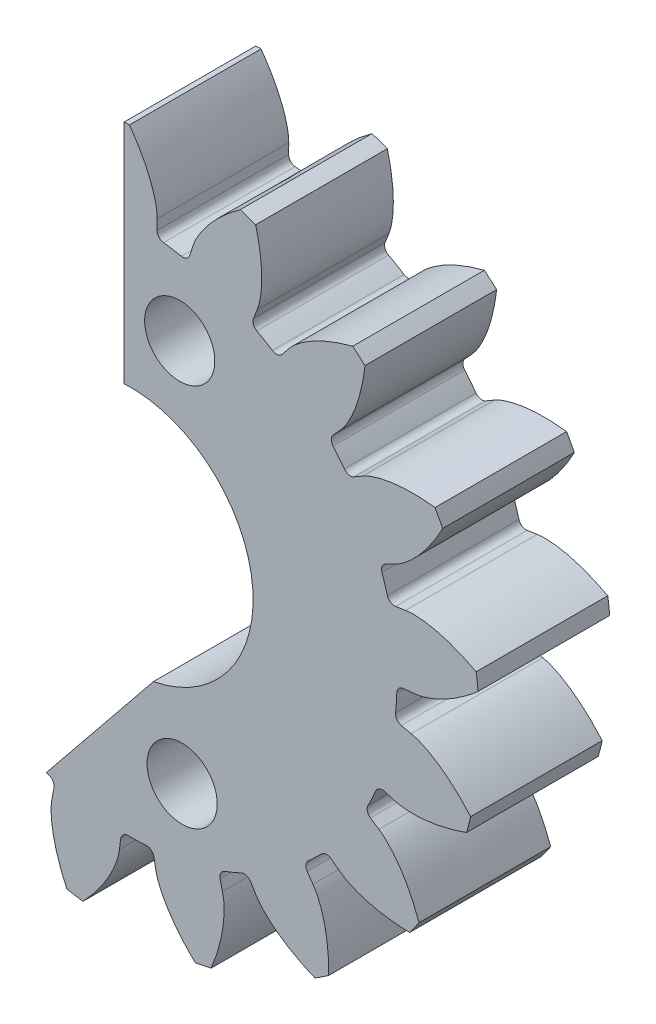
SolidWorks part; units mm, degrees
ref_plane "Front" through (0, 0, 0) normal (0, 0, 1) x (1, 0, 0)
ref_plane "Top" through (0, 0, 0) normal (0, 1, 0) x (1, 0, 0)
ref_plane "Right" through (0, 0, 0) normal (1, 0, 0) x (0, 0, -1)
sketch "Sketch1" plane through (0, 0, 0) normal (0, 0, 1) x (1, 0, 0)
  line L68 (2.1427, 9.4464) -> (2.0368, 9.1165)
  line L69 (0.916, 9.2963) -> (0.9185, 9.6427)
  line L70 (-1.4144, 9.5825) -> (-1.394, 9.2367)
  line L71 (-2.504, 8.9994) -> (-2.6268, 9.3234)
  line L72 (-4.7805, 8.4245) -> (-4.6366, 8.1093)
  line L73 (-5.5859, 7.4871) -> (-5.8174, 7.7449)
  line L74 (-7.501, 6.1287) -> (-7.2529, 5.8868)
  line L75 (-7.9134, 4.9637) -> (-8.2224, 5.1204)
  line L76 (-9.2084, 3.0052) -> (-8.8897, 2.8692)
  line L77 (-9.1721, 1.7699) -> (-9.5168, 1.8043)
  line L78 (-9.6722, -0.5242) -> (-9.3259, -0.5358)
  line L79 (-9.1921, -1.663) -> (-9.526, -1.7554)
  line L80 (-8.8296, -3.9828) -> (-8.5026, -3.8686)
  line L81 (-7.9706, -4.8713) -> (-8.2486, -5.078)
  line L82 (-6.7946, -6.9035) -> (-6.5309, -6.6788)
  line L83 (-5.6727, -7.4216) -> (-5.8572, -7.7148)
  line L84 (-3.842, -8.8918) -> (-3.6772, -8.587)
  line L85 (-2.6086, -8.9696) -> (-2.6747, -9.3097)
  line L86 (-0.3704, -9.6793) -> (-0.3269, -9.3356)
  line L87 (0.8078, -9.3063) -> (0.8689, -9.6473)
  line L88 (3.1511, -9.1595) -> (3.0675, -8.8232)
  line L89 (4.115, -8.3861) -> (4.2953, -8.6819)
  line L90 (6.2471, -7.4026) -> (6.0477, -7.1193)
  line L91 (6.8665, -6.3332) -> (7.1415, -6.544)
  line L92 (8.4994, -4.646) -> (8.2111, -4.4539)
  line L93 (8.6907, -3.4251) -> (9.0232, -3.5223)
  line L94 (9.6038, -1.2619) -> (9.2656, -1.1869)
  line L95 (9.3411, -0.0544) -> (9.6863, -0.0249)
  line L96 (9.4111, 2.2926) -> (9.0686, 2.2404)
  line L97 (8.73, 3.3237) -> (9.0412, 3.4759)
  line L98 (7.9475, 5.5374) -> (7.6469, 5.365)
  line L99 (6.9398, 6.2529) -> (7.1751, 6.5072)
  line L100 (5.4104, 8.0345) -> (5.1925, 7.7651)
  line L101 (4.2123, 8.3376) -> (4.3399, 8.6597)
  circle A0 centre (0, 0) radius 1.5
  arc A136 (4.2867, 11.1494) -> (3.764, 11.3366) centre (0, 0) ccw
  arc A137 (1.7491, 8.9466) -> (2.0368, 9.1165) centre (1.7973, 9.1934) ccw
  arc A138 (1.7491, 8.9466) -> (1.1361, 9.0449) centre (0, 0) ccw
  arc A139 (0.916, 9.2963) -> (1.1361, 9.0449) centre (1.1675, 9.2944) ccw
  arc A140 (-0.0304, 11.945) -> (-0.5854, 11.9307) centre (0, 0) ccw
  arc A141 (-1.6009, 8.9743) -> (-1.394, 9.2367) centre (-1.6451, 9.2219) ccw
  arc A142 (-1.6009, 8.9743) -> (-2.208, 8.8445) centre (0, 0) ccw
  arc A143 (-2.504, 8.9994) -> (-2.208, 8.8445) centre (-2.2689, 9.0885) ccw
  arc A144 (-4.3434, 11.1274) -> (-4.8558, 10.9136) centre (0, 0) ccw
  arc A145 (-4.7347, 7.79) -> (-4.6366, 8.1093) centre (-4.8653, 8.0049) ccw
  arc A146 (-4.7347, 7.79) -> (-5.2539, 7.4497) centre (0, 0) ccw
  arc A147 (-5.5859, 7.4871) -> (-5.2539, 7.4497) centre (-5.3988, 7.6552) ccw
  arc A148 (-8.0698, 8.807) -> (-8.4703, 8.4225) centre (0, 0) ccw
  arc A149 (-7.229, 5.5536) -> (-7.2529, 5.8868) centre (-7.4285, 5.7068) ccw
  arc A150 (-7.229, 5.5536) -> (-7.5902, 5.0487) centre (0, 0) ccw
  arc A151 (-7.9134, 4.9637) -> (-7.5902, 5.0487) centre (-7.7996, 5.188) ccw
  arc A152 (-10.7063, 5.2971) -> (-10.9409, 4.7939) centre (0, 0) ccw
  arc A153 (-8.7471, 2.5671) -> (-8.8897, 2.8692) centre (-8.9884, 2.6379) ccw
  arc A154 (-8.7471, 2.5671) -> (-8.9015, 1.9659) centre (0, 0) ccw
  arc A155 (-9.1721, 1.7699) -> (-8.9015, 1.9659) centre (-9.147, 2.0201) ccw
  arc A156 (-11.8969, 1.0719) -> (-11.9338, 0.5179) centre (0, 0) ccw
  arc A157 (-9.0837, -0.766) -> (-9.3259, -0.5358) centre (-9.3343, -0.7872) ccw
  arc A158 (-9.0837, -0.766) -> (-9.0105, -1.3825) centre (0, 0) ccw
  arc A159 (-9.1921, -1.663) -> (-9.0105, -1.3825) centre (-9.2591, -1.4206) ccw
  arc A160 (-11.4807, -3.2982) -> (-11.3151, -3.8281) centre (0, 0) ccw
  arc A161 (-8.1936, -3.9957) -> (-8.5026, -3.8686) centre (-8.4196, -4.106) ccw
  arc A162 (-8.1936, -3.9957) -> (-7.9027, -4.5441) centre (0, 0) ccw
  arc A163 (-7.9706, -4.8713) -> (-7.9027, -4.5441) centre (-8.1207, -4.6695) ccw
  arc A164 (-9.514, -7.2228) -> (-9.1681, -7.6571) centre (0, 0) ccw
  arc A165 (-6.1969, -6.6858) -> (-6.5309, -6.6788) centre (-6.3678, -6.8702) ccw
  arc A166 (-6.1969, -6.6858) -> (-5.7275, -7.092) centre (0, 0) ccw
  arc A167 (-5.6727, -7.4216) -> (-5.7275, -7.092) centre (-5.8855, -7.2877) ccw
  arc A168 (-6.2624, -10.1719) -> (-5.783, -10.4519) centre (0, 0) ccw
  arc A169 (-3.3632, -8.4729) -> (-3.6772, -8.587) centre (-3.456, -8.7066) ccw
  arc A170 (-3.3632, -8.4729) -> (-2.7788, -8.6821) centre (0, 0) ccw
  arc A171 (-2.6086, -8.9696) -> (-2.7788, -8.6821) centre (-2.8554, -8.9216) ccw
  arc A172 (-2.165, -11.7472) -> (-1.6168, -11.8352) centre (0, 0) ccw
  arc A173 (-0.0754, -9.1157) -> (-0.3269, -9.3356) centre (-0.0774, -9.3671) ccw
  arc A174 (-0.0754, -9.1157) -> (0.5452, -9.0997) centre (0, 0) ccw
  arc A175 (0.8078, -9.3063) -> (0.5452, -9.0997) centre (0.5602, -9.3507) ccw
  arc A176 (2.2248, -11.7361) -> (2.7677, -11.62) centre (0, 0) ccw
  arc A177 (3.2227, -8.5273) -> (3.0675, -8.8232) centre (3.3116, -8.7626) ccw
  arc A178 (3.2227, -8.5273) -> (3.7956, -8.2882) centre (0, 0) ccw
  arc A179 (4.115, -8.3861) -> (3.7956, -8.2882) centre (3.9003, -8.5169) ccw
  arc A180 (6.3141, -10.1399) -> (6.7785, -9.8355) centre (0, 0) ccw
  arc A181 (6.0855, -6.7873) -> (6.0477, -7.1193) centre (6.2534, -6.9746) ccw
  arc A182 (6.0855, -6.7873) -> (6.5333, -6.3574) centre (0, 0) ccw
  arc A183 (6.8665, -6.3332) -> (6.5333, -6.3574) centre (6.7135, -6.5328) ccw
  arc A184 (9.5507, -7.1742) -> (9.8737, -6.7227) centre (0, 0) ccw
  arc A185 (8.1264, -4.1307) -> (8.2111, -4.4539) centre (8.3506, -4.2446) ccw
  arc A186 (8.1264, -4.1307) -> (8.3887, -3.568) centre (0, 0) ccw
  arc A187 (8.6907, -3.4251) -> (8.3887, -3.568) centre (8.6201, -3.6665) ccw
  arc A188 (11.4974, -3.2397) -> (11.6355, -2.7019) centre (0, 0) ccw
  arc A189 (9.0698, -0.9161) -> (9.2656, -1.1869) centre (9.32, -0.9414) ccw
  arc A190 (9.0698, -0.9161) -> (9.1112, -0.2967) centre (0, 0) ccw
  arc A191 (9.3411, -0.0544) -> (9.1112, -0.2967) centre (9.3625, -0.3049) ccw
  arc A192 (11.8913, 1.1324) -> (11.8258, 1.6838) centre (0, 0) ccw
  arc A193 (8.7883, 2.4221) -> (9.0686, 2.2404) centre (9.0307, 2.489) ccw
  arc A194 (8.7883, 2.4221) -> (8.6031, 3.0146) centre (0, 0) ccw
  arc A195 (8.73, 3.3237) -> (8.6031, 3.0146) centre (8.8404, 3.0978) ccw
  arc A196 (10.6792, 5.3516) -> (10.419, 5.842) centre (0, 0) ccw
  arc A197 (7.3199, 5.4333) -> (7.6469, 5.365) centre (7.5218, 5.5832) ccw
  arc A198 (7.3199, 5.4333) -> (6.9331, 5.9189) centre (0, 0) ccw
  arc A199 (6.9398, 6.2529) -> (6.9331, 5.9189) centre (7.1244, 6.0821) ccw
  arc A200 (8.0248, 8.848) -> (7.605, 9.2113) centre (0, 0) ccw
  arc A201 (4.8629, 7.7106) -> (5.1925, 7.7651) centre (4.997, 7.9233) ccw
  arc A202 (4.8629, 7.7106) -> (4.3268, 8.0237) centre (0, 0) ccw
  arc A203 (4.2123, 8.3376) -> (4.3268, 8.0237) centre (4.4462, 8.245) ccw
  spline S68 degree 3 poles (3.764, 11.3366) (3.2587, 10.9714) (2.6231, 10.3935) (2.2067, 9.6531) (2.1427, 9.4464) knots -0.008485 -0.008485 -0.008485 -0.008485 0.741457 1 1 1 1
  spline S69 degree 3 poles (0.9185, 9.6427) (0.9201, 9.8535) (0.7567, 10.6863) (0.3366, 11.435) (-0.0304, 11.945) knots 0 0 0 0 0.250058 1 1 1 1
  spline S70 degree 3 poles (-0.5854, 11.9307) (-0.9247, 11.4077) (-1.3085, 10.6392) (-1.4294, 9.7984) (-1.4144, 9.5825) knots -0.008485 -0.008485 -0.008485 -0.008485 0.741457 1 1 1 1
  spline S71 degree 3 poles (-2.6268, 9.3234) (-2.7015, 9.5204) (-3.1547, 10.238) (-3.8169, 10.7844) (-4.3434, 11.1274) knots 0 0 0 0 0.250058 1 1 1 1
  spline S72 degree 3 poles (-4.8558, 10.9136) (-4.9832, 10.3033) (-5.0635, 9.4481) (-4.8725, 8.6204) (-4.7805, 8.4245) knots -0.008485 -0.008485 -0.008485 -0.008485 0.741457 1 1 1 1
  spline S73 degree 3 poles (-5.8174, 7.7449) (-5.9583, 7.9016) (-6.64, 8.4071) (-7.455, 8.6773) (-8.0698, 8.807) knots 0 0 0 0 0.250058 1 1 1 1
  spline S74 degree 3 poles (-8.4703, 8.4225) (-8.3687, 7.8074) (-8.1346, 6.9809) (-7.6575, 6.2781) (-7.501, 6.1287) knots -0.008485 -0.008485 -0.008485 -0.008485 0.741457 1 1 1 1
  spline S75 degree 3 poles (-8.2224, 5.1204) (-8.4103, 5.2157) (-9.2286, 5.4407) (-10.0862, 5.3983) (-10.7063, 5.2971) knots 0 0 0 0 0.250058 1 1 1 1
  spline S76 degree 3 poles (-10.9409, 4.7939) (-10.624, 4.2571) (-10.1071, 3.5709) (-9.4083, 3.088) (-9.2084, 3.0052) knots -0.008485 -0.008485 -0.008485 -0.008485 0.741457 1 1 1 1
  spline S77 degree 3 poles (-9.5168, 1.8043) (-9.7265, 1.8253) (-10.5708, 1.7395) (-11.3552, 1.3902) (-11.8969, 1.0719) knots 0 0 0 0 0.250058 1 1 1 1
  spline S78 degree 3 poles (-11.9338, 0.5179) (-11.4444, 0.1318) (-10.7145, -0.3213) (-9.8885, -0.5192) (-9.6722, -0.5242) knots -0.008485 -0.008485 -0.008485 -0.008485 0.741457 1 1 1 1
  spline S79 degree 3 poles (-9.526, -1.7554) (-9.7291, -1.8116) (-10.4854, -2.1966) (-11.0906, -2.8056) (-11.4807, -3.2982) knots 0 0 0 0 0.250058 1 1 1 1
  spline S80 degree 3 poles (-11.3151, -3.8281) (-10.7192, -4.0113) (-9.875, -4.1701) (-9.0332, -4.0563) (-8.8296, -3.9828) knots -0.008485 -0.008485 -0.008485 -0.008485 0.741457 1 1 1 1
  spline S81 degree 3 poles (-8.2486, -5.078) (-8.4177, -5.2038) (-8.9839, -5.836) (-9.3281, -6.6225) (-9.514, -7.2228) knots 0 0 0 0 0.250058 1 1 1 1
  spline S82 degree 3 poles (-9.1681, -7.6571) (-8.5463, -7.6126) (-7.7017, -7.4558) (-6.9579, -7.0456) (-6.7946, -6.9035) knots -0.008485 -0.008485 -0.008485 -0.008485 0.741457 1 1 1 1
  spline S83 degree 3 poles (-5.8572, -7.7148) (-5.9694, -7.8932) (-6.269, -8.6873) (-6.3059, -9.545) (-6.2624, -10.1719) knots 0 0 0 0 0.250058 1 1 1 1
  spline S84 degree 3 poles (-5.783, -10.4519) (-5.2192, -10.1859) (-4.4883, -9.7345) (-3.9429, -9.0833) (-3.842, -8.8918) knots -0.008485 -0.008485 -0.008485 -0.008485 0.741457 1 1 1 1
  spline S85 degree 3 poles (-2.6747, -9.3097) (-2.715, -9.5166) (-2.7074, -10.3653) (-2.432, -11.1784) (-2.165, -11.7472) knots 0 0 0 0 0.250058 1 1 1 1
  spline S86 degree 3 poles (-1.6168, -11.8352) (-1.1872, -11.3834) (-0.6687, -10.6985) (-0.3954, -9.8942) (-0.3704, -9.6793) knots -0.008485 -0.008485 -0.008485 -0.008485 0.741457 1 1 1 1
  spline S87 degree 3 poles (0.8689, -9.6473) (0.9062, -9.8547) (1.2197, -10.6434) (1.7703, -11.3021) (2.2248, -11.7361) knots 0 0 0 0 0.250058 1 1 1 1
  spline S88 degree 3 poles (2.7677, -11.62) (3.0051, -11.0436) (3.2412, -10.2176) (3.2055, -9.3689) (3.1511, -9.1595) knots -0.008485 -0.008485 -0.008485 -0.008485 0.741457 1 1 1 1
  spline S89 degree 3 poles (4.2953, -8.6819) (4.4049, -8.8619) (4.9822, -9.484) (5.7336, -9.8994) (6.3141, -10.1399) knots 0 0 0 0 0.250058 1 1 1 1
  spline S90 degree 3 poles (6.7785, -9.8355) (6.7916, -9.2122) (6.7134, -8.3568) (6.3735, -7.5783) (6.2471, -7.4026) knots -0.008485 -0.008485 -0.008485 -0.008485 0.741457 1 1 1 1
  spline S91 degree 3 poles (7.1415, -6.544) (7.3088, -6.6723) (8.0718, -7.0438) (8.9225, -7.1597) (9.5507, -7.1742) knots 0 0 0 0 0.250058 1 1 1 1
  spline S92 degree 3 poles (9.8737, -6.7227) (9.6608, -6.1367) (9.2788, -5.3673) (8.6807, -4.7642) (8.4994, -4.646) knots -0.008485 -0.008485 -0.008485 -0.008485 0.741457 1 1 1 1
  spline S93 degree 3 poles (9.0232, -3.5223) (9.2255, -3.5815) (10.0712, -3.6523) (10.9064, -3.4531) (11.4974, -3.2397) knots 0 0 0 0 0.250058 1 1 1 1
  spline S94 degree 3 poles (11.6355, -2.7019) (11.2253, -2.2324) (10.5911, -1.653) (9.8155, -1.3066) (9.6038, -1.2619) knots -0.008485 -0.008485 -0.008485 -0.008485 0.741457 1 1 1 1
  spline S95 degree 3 poles (9.6863, -0.0249) (9.8963, -0.007) (10.7105, 0.2325) (11.4173, 0.7199) (11.8913, 1.1324) knots 0 0 0 0 0.250058 1 1 1 1
  spline S96 degree 3 poles (11.8258, 1.6838) (11.2737, 1.9734) (10.4731, 2.2846) (9.6247, 2.3274) (9.4111, 2.2926) knots -0.008485 -0.008485 -0.008485 -0.008485 0.741457 1 1 1 1
  spline S97 degree 3 poles (9.0412, 3.4759) (9.2306, 3.5684) (9.9033, 4.0859) (10.3862, 4.7957) (10.6792, 5.3516) knots 0 0 0 0 0.250058 1 1 1 1
  spline S98 degree 3 poles (10.419, 5.842) (9.7996, 5.9126) (8.9406, 5.9136) (8.134, 5.6471) (7.9475, 5.5374) knots -0.008485 -0.008485 -0.008485 -0.008485 0.741457 1 1 1 1
  spline S99 degree 3 poles (7.1751, 6.5072) (7.3182, 6.6619) (7.7585, 7.3874) (7.9524, 8.2238) (8.0248, 8.848) knots 0 0 0 0 0.250058 1 1 1 1
  spline S100 degree 3 poles (7.605, 9.2113) (7.002, 9.0534) (6.2006, 8.744) (5.5448, 8.2041) (5.4104, 8.0345) knots -0.008485 -0.008485 -0.008485 -0.008485 0.741457 1 1 1 1
  spline S101 degree 3 poles (4.3399, 8.6597) (4.4174, 8.8557) (4.566, 9.6913) (4.4446, 10.5412) (4.2867, 11.1494) knots 0 0 0 0 0.250058 1 1 1 1
  dimension "D1" = 3
extrude "Boss-Extrude1" add sketch "Sketch1" along normal blind 4.5
sketch "Sketch3" plane through (0, 0, 4.5) normal (0, 0, 1) x (1, 0, 0)
  line L0 (0, 0) -> (-24.6444, 0)
sketch "Sketch4" plane through (0, 0, 0) normal (0, 0, -1) x (-1, 0, 0)
  line L0 (12.8632, 15.1898) -> (0.2099, 15.1898)
  line L1 (3.0728, -8.5825) -> (3.0728, -14.2917) construction
  line L2 (3.0728, -14.2917) -> (12.6632, -14.2917) construction
  line L4 (3.0728, -8.5825) -> (-0.6826, -3.9413) construction
  line L5 (12.6632, -14.2917) -> (12.6632, 14.9898) construction
  line L6 (12.6632, 14.9898) -> (0.4099, 14.9898) construction
  line L7 (0.2099, 15.1898) -> (0.2099, 4.1947)
  line L8 (2.8728, -8.6533) -> (-0.7915, -4.1248)
  line L9 (2.8728, -8.6533) -> (2.8728, -14.4917)
  line L10 (2.8728, -14.4917) -> (12.8632, -14.4917)
  line L11 (12.8632, -14.4917) -> (12.8632, 15.1898)
  line L22 (0.4099, 14.9898) -> (0.4099, 3.9789) construction
  arc A0 (0.2099, 4.1947) -> (-0.7915, -4.1248) centre (0, 0) ccw
  arc A3 (0.4099, 3.9789) -> (-0.6826, -3.9413) centre (0, 0) ccw construction
  dimension "D1" = 0.2
extrude "Cut-Extrude1" cut sketch "Sketch4" against normal through all
sketch "Sketch5" plane through (0, 0, 4.5) normal (0, 0, 1) x (1, 0, 0)
  line L1 (-0.2099, 11.9432) -> (-0.2099, 4.1947) construction
  circle A2 centre (1.6901, 6.4124) radius 1
  circle A3 centre (1.7728, -6.6584) radius 1
  dimension "D1" = 2
  dimension "D2" = 1.9
hole_wizard "CSK for M2 Countersunk Flat Head Screw1" positions "Sketch7" profile "Sketch8" countersink size "M2" standard "ISO"
sketch "Sketch7" plane through (0, 0, 0) normal (0, 0, 1) x (1, 0, 0)
  point P0 (1.6901, 6.4124)
  point P2 (1.7728, -6.6584)
  point P19 (0, 0)
  point P20 (0, 0)
  point P21 (1.7728, -6.6584)
  point P23 (0, 0)
  point P24 (1.7728, -6.6584)
  dimension "D1" = 1.6901
  dimension "D2" = 6.4124
  dimension "D3" = 1.7728
  dimension "D4" = 6.6584
sketch "Sketch8" plane through (1.6901, 6.4124, 0) normal (1, 0, 0) x (0, 1, 0)
  line L0 (0, 0) -> (0, 10.721)
  line L1 (0, 10.721) -> (1.2, 10)
  line L2 (1.2, 10) -> (1.2, 1)
  line L3 (1.2, 1) -> (2.2, 0)
  line L5 (2.2, 0) -> (0, 0)
  line L6 (-1.2, 1) -> (-2.2, 0) construction
  line L10 (0, 10.721) -> (-1.2, 10) construction
  line L11 (0, -6.35) -> (0, 107.95) construction
  dimension "Hole Dia." = 2.4
  dimension "Hole Depth" = 10
  dimension "Near C'Sink Dia." = 4.4
  dimension "Near C'Sink Angle" = 90
  dimension "Drill Angle" = 118
